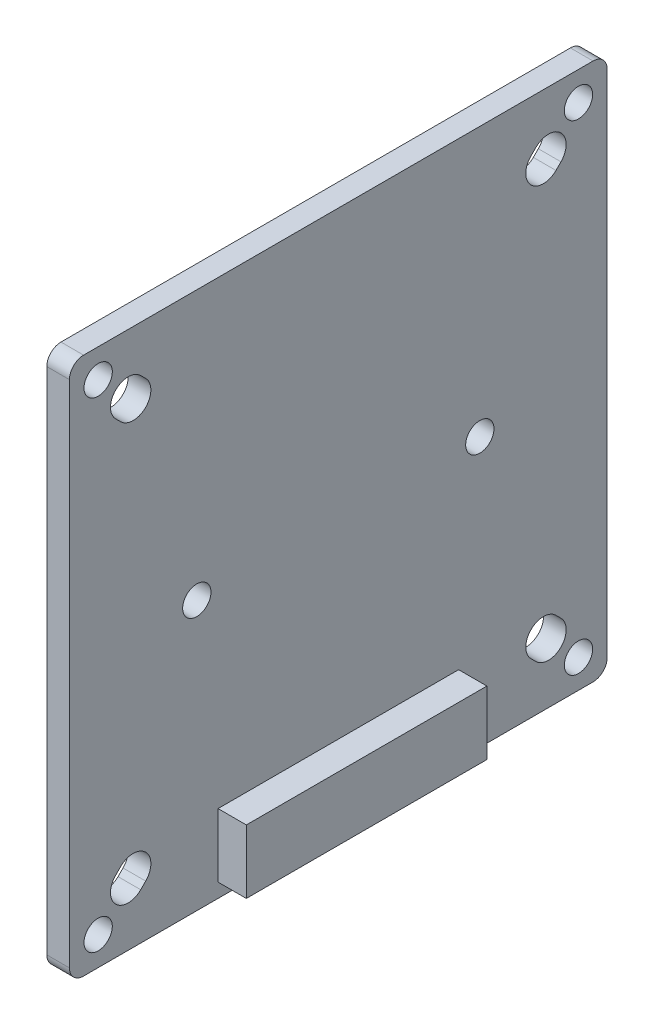
SolidWorks part; units mm, degrees
material "Circuit imprimé d'alimentation"
ref_plane "Plan XY" through (0, 0, 0) normal (0, 0, 1) x (1, 0, 0)
ref_plane "Plan ZX" through (0, 0, 0) normal (0, 1, 0) x (1, 0, 0)
ref_plane "Plan YZ" through (0, 0, 0) normal (1, 0, 0) x (0, 0, -1)
sketch "Esquisse1" plane through (0, 0, 0) normal (1, 0, 0) x (0, 0, -1)
  line L1 (19, -19) -> (-19, -19)
  line L2 (19, -19) -> (19, 19)
  line L3 (19, 19) -> (-19, 19)
  line L4 (-19, -19) -> (-19, 19)
  line L5 (19, -19) -> (-19, 19) construction
  line L6 (19, 19) -> (-19, -19) construction
  point P0 (0, 0)
  dimension "D1" = 38
extrude "Boss.-Extru.1" add sketch "Esquisse1" along normal blind 1.6
fillet "Congé1" radius 1 4 edges at (0.8, -19, 19) (0.8, -19, -19) (0.8, 19, -19) (0.8, 19, 19)
sketch "Esquisse2" plane through (1.6, 0, 0) normal (1, 0, 0) x (0, 0, -1)
  line L0 (-10, 0) -> (10, 0) construction
  circle A0 centre (-10, 0) radius 1
  circle A1 centre (10, 0) radius 1
  dimension "D1" = 20
  dimension "D2" = 2
extrude "Enlèv. mat.-Extru.1" cut sketch "Esquisse2" against normal through all
sketch "Esquisse3" plane through (1.6, 0, 0) normal (1, 0, 0) x (0, 0, -1)
  line L0 (14.4957, 14.4957) -> (14.8492, 14.8492) construction
  line L1 (13.6118, 15.3796) -> (13.9654, 15.7331)
  line L2 (15.3796, 13.6118) -> (15.7331, 13.9654)
  line L3 (0, 0) -> (14.4957, 14.4957) construction
  line L4 (0.88, 0) -> (-0.88, 0) construction
  line L5 (14.6725, 14.6725) -> (16.9706, 16.9706) construction
  arc A0 (13.6118, 15.3796) -> (15.3796, 13.6118) centre (14.4957, 14.4957) ccw
  arc A1 (15.7331, 13.9654) -> (13.9654, 15.7331) centre (14.8492, 14.8492) ccw
  circle A2 centre (16.9706, 16.9706) radius 1
  point P2 (14.6725, 14.6725)
  point P11 (17.0121, 17.0121)
  dimension "D5" = 2
  dimension "D1" = 2.5
  dimension "D2" = 20.75
  dimension "D3" = 45
  dimension "D4" = 0.5
  dimension "D6" = 24
extrude "Enlèv. mat.-Extru.2" cut sketch "Esquisse3" against normal through all
ref_axis "Axe1" through (9.4017, 0, 0) along (-1, 0, 0)
pattern_circular "Répétition circulaire1" count 4 over 360 about axis through (9.4017, 0, 0) along (-1, 0, 0) of "Enlèv. mat.-Extru.2"
sketch "Esquisse4" plane through (1.6, 0, 0) normal (1, 0, 0) x (0, 0, -1)
  line L0 (0, -13.5) -> (0, 0) construction
  line L1 (-8.5, -18) -> (8.5, -18)
  line L2 (-8.5, -18) -> (-8.5, -13.5)
  line L3 (-8.5, -13.5) -> (8.5, -13.5)
  line L4 (8.5, -18) -> (8.5, -13.5)
  line L5 (-18, -19) -> (18, -19) construction
  dimension "D1" = 4.5
  dimension "D2" = 17
  dimension "D3" = 1
extrude "Boss.-Extru.2" add sketch "Esquisse4" along normal blind 2
